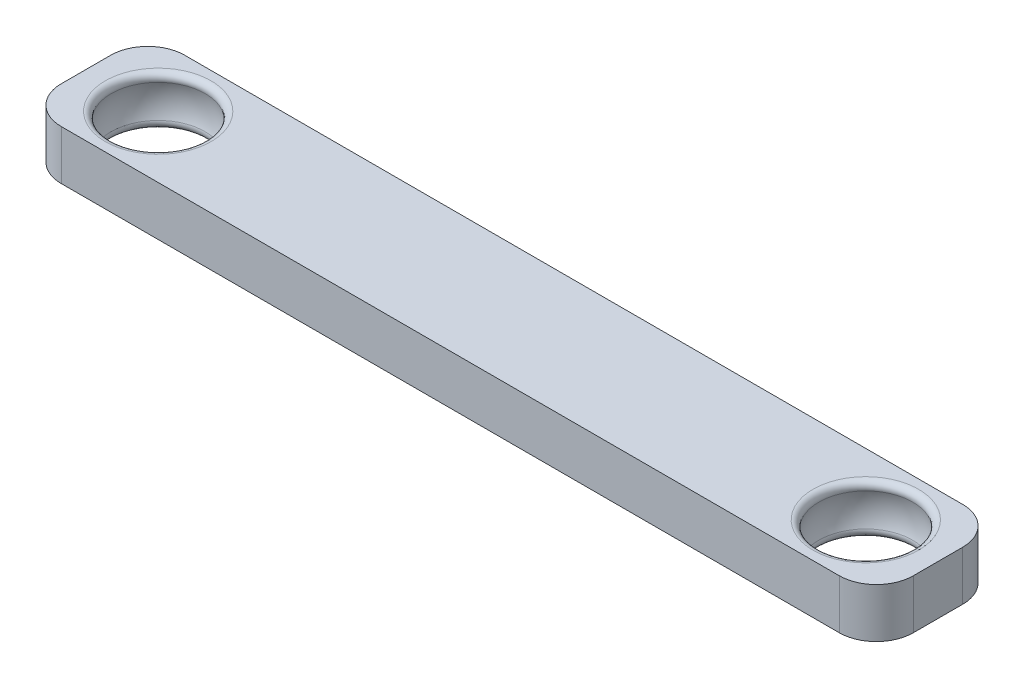
SolidWorks part; units mm, degrees
ref_plane "Front Plane" through (0, 0, 0) normal (0, 0, 1) x (1, 0, 0)
ref_plane "Top Plane" through (0, 0, 0) normal (0, 1, 0) x (1, 0, 0)
ref_plane "Right Plane" through (0, 0, 0) normal (1, 0, 0) x (0, 0, -1)
sketch "Sketch1" plane through (0, 0, 0) normal (0, 1, 0) x (1, 0, 0)
  line L1 (-34.5, 5) -> (34.5, 5)
  line L2 (-34.5, 5) -> (-34.5, -5)
  line L3 (-34.5, -5) -> (34.5, -5)
  line L4 (34.5, 5) -> (34.5, -5)
  line L5 (-34.5, 5) -> (34.5, -5) construction
  line L6 (-34.5, -5) -> (34.5, 5) construction
  point P0 (0, 0)
  dimension "D1" = 10
  dimension "D2" = 69
extrude "Boss-Extrude1" add sketch "Sketch1" along normal blind 4
sketch "Sketch2" plane through (0, 0, 0) normal (0, 0, 1) x (1, 0, 0)
  line L0 (-28.65, 4) -> (-28.65, 0)
  line L1 (-34.5, 4) -> (34.5, 4) construction
  line L2 (-34.5, 0) -> (34.5, 0) construction
  line L3 (-28.65, 4) -> (-32.15, 4)
  line L4 (-28.65, 0) -> (-32.15, 0)
  arc A0 (-32.15, 4) -> (-32.15, 0) centre (-28.65, 2) ccw
  dimension "D1" = 28.65
  dimension "D2" = 3.5
revolve "Cut-Revolve2" cut sketch "Sketch2" angle 360 about L0
fillet "Fillet1" radius 3 4 edges at (34.5, 2, -5) (34.5, 2, 5) (-34.5, 2, -5) (-34.5, 2, 5)
mirror "Mirror1" about plane through (0, 0, 0) normal (1, 0, 0) of "Cut-Revolve2"
fillet "Fillet2" radius 0.5 4 edges at (-28.65, 0, 3.5) (28.65, 0, 3.5) (28.65, 4, 3.5) (-28.65, 4, 3.5)
